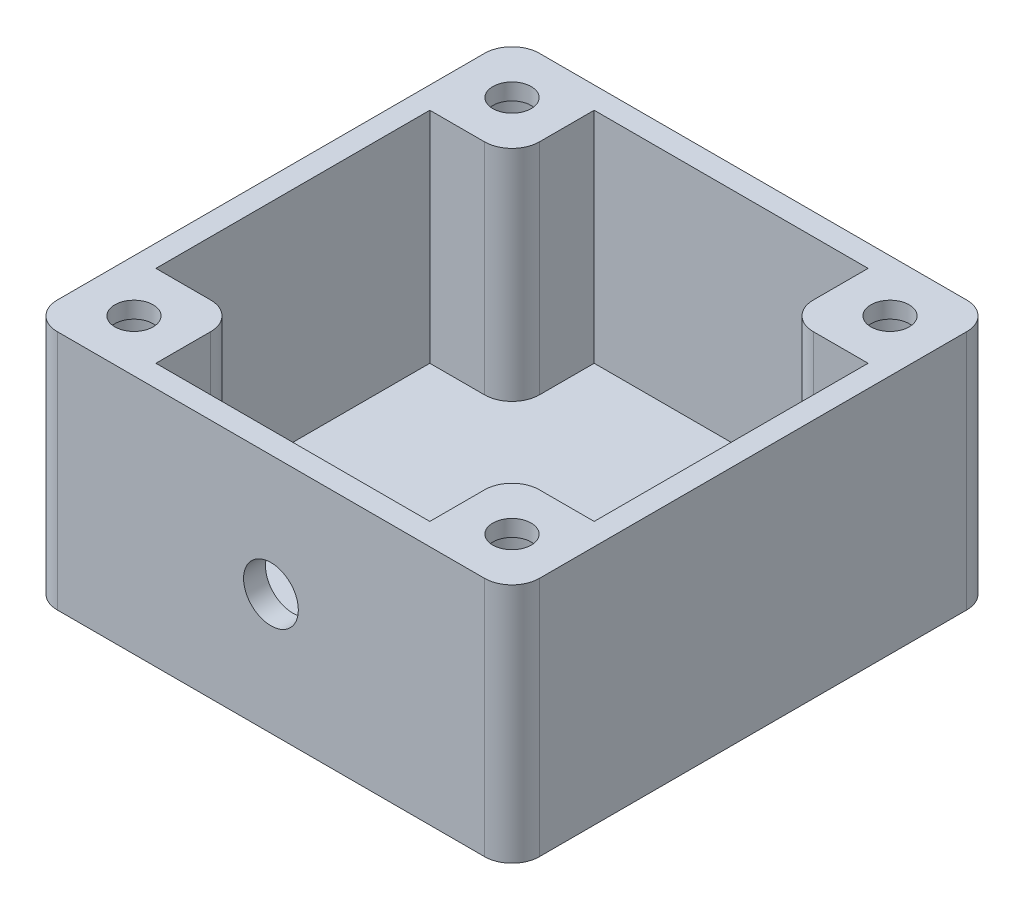
SolidWorks part; units mm, degrees
ref_plane "Front" through (0, 0, 0) normal (0, 0, 1) x (1, 0, 0)
ref_plane "Top" through (0, 0, 0) normal (0, 1, 0) x (1, 0, 0)
ref_plane "Right" through (0, 0, 0) normal (1, 0, 0) x (0, 0, -1)
sketch "Sketch1" plane through (0, 0, 0) normal (0, 1, 0) x (1, 0, 0)
  line L1 (-12.5, -20) -> (12.5, -20)
  line L2 (-12.5, -20) -> (-12.5, 20)
  line L3 (-12.5, 20) -> (12.5, 20)
  line L4 (12.5, -20) -> (12.5, 20)
  line L5 (-12.5, -20) -> (12.5, 20) construction
  line L6 (-12.5, 20) -> (12.5, -20) construction
  line L7 (-22, -22) -> (22, -22)
  line L8 (-22, -22) -> (-22, 22)
  line L9 (-22, 22) -> (22, 22)
  line L10 (22, -22) -> (22, 22)
  line L11 (-22, -22) -> (22, 22) construction
  line L12 (-22, 22) -> (22, -22) construction
  point P0 (0, 0)
  point P10 (0, 0)
  dimension "45" = 40
  dimension "D6" = 25
  dimension "D7" = 9.5
  dimension "D8" = 2
extrude "Boss-Extrude4" add sketch "Sketch1" along normal blind 20
sketch "Sketch4" plane through (0, 0, 0) normal (0, -1, 0) x (1, 0, 0)
  line L1 (22, -22) -> (-22, -22)
  line L2 (22, -22) -> (22, 22)
  line L3 (22, 22) -> (-22, 22)
  line L4 (-22, -22) -> (-22, 22)
  line L5 (22, -22) -> (-22, 22) construction
  line L6 (22, 22) -> (-22, -22) construction
  point P0 (0, 0)
extrude "Boss-Extrude5" add sketch "Sketch4" along normal blind 2
sketch "Sketch5" plane through (0, 0, 0) normal (0, 1, 0) x (1, 0, 0)
  line L0 (-3.8714, -6.8383) -> (-1.43, -7.7269)
  line L1 (0, 0) -> (0, -18.2319) construction
  line L2 (0, 0) -> (-2.9072, -7.9874) construction
  circle A0 centre (0, 0) radius 3.45
  arc A1 (-3.8714, -6.8383) -> (-1.43, -7.7269) centre (-2.9072, -7.9874) ccw
  dimension "D1" = 6.9
  dimension "D3" = 3
  dimension "D2" = 8.5
  dimension "D5" = 0.75
  dimension "D4" = 20
extrude "Cut-Extrude2" cut sketch "Sketch5" against normal blind 2
sketch "Sketch6" plane through (0, 20, 0) normal (0, 1, 0) x (1, 0, 0)
  line L0 (0, 22) -> (0, -22) construction
  line L1 (22, 22) -> (-22, 22) construction
  line L2 (-22, -22) -> (22, -22) construction
  line L3 (-12.5, -20) -> (-22, -20) construction
  line L4 (-22, 22) -> (-22, -22) construction
  line L5 (-17.25, -20) -> (-17.25, 22) construction
  circle A0 centre (-17.25, 17.25) radius 1.75
  circle A1 centre (-17.25, -17.25) radius 1.75
  dimension "D2" = 3.5
  dimension "D1" = 4.75
  dimension "D3" = 4.75
  dimension "D4" = 4.75
extrude "Cut-Extrude3" cut sketch "Sketch6" against normal through all
mirror "Mirror1" about plane through (0, 0, 0) normal (1, 0, 0) of "Cut-Extrude3"
sketch "Sketch7" plane through (0, -2, 0) normal (0, -1, 0) x (1, 0, 0)
  circle A0 centre (-17.25, 17.25) radius 3.25
  circle A1 centre (17.25, 17.25) radius 3.25
  circle A2 centre (17.25, -17.25) radius 3.25
  circle A3 centre (-17.25, -17.25) radius 3.25
  point P11 (-17.25, -17.25)
  point P13 (-17.25, -17.25)
  point P14 (-17.25, -17.25)
  point P15 (-18.5, -18.5)
  point P16 (0, 0)
  point P17 (0, 0)
  point P18 (-22.25, -22.25)
  point P20 (0, 0)
  point P21 (0, 0)
  dimension "D1" = 6.5
extrude "Cut-Extrude4" cut sketch "Sketch7" against normal offset from surface (20.5 mm away) 1.5 up to face at (17.25, 20, -15.5)
sketch "Sketch10" plane through (0, 20, 0) normal (0, 1, 0) x (1, 0, 0)
  line L0 (-12.5, 20) -> (-12.5, -20) construction
  line L1 (-12.5, 12.5) -> (-20, 12.5)
  line L2 (-12.5, 12.5) -> (-12.5, -12.5)
  line L3 (-12.5, -12.5) -> (-20, -12.5)
  line L4 (-20, 12.5) -> (-20, -12.5)
  line L5 (-22, 22) -> (-22, -22) construction
  line L7 (-22, 22) -> (22, 22) construction
  line L8 (12.5, 20) -> (-12.5, 20) construction
  circle A0 centre (-17.25, 17.25) radius 1.75 construction
  circle A1 centre (-17.25, -17.25) radius 1.75 construction
  dimension "D3" = 4.75
  dimension "D1" = 2
  dimension "D2" = 2
  dimension "D4" = 4.75
  dimension "D5" = 4.75
extrude "Cut-Extrude5" cut sketch "Sketch10" against normal up to surface (20 mm away) up to face at (0, 0, 3.45)
mirror "Mirror2" about plane through (0, 0, 0) normal (1, 0, 0) of "Cut-Extrude5"
sketch "Sketch11" plane through (0, 0, 22) normal (0, 0, 1) x (1, 0, 0)
  line L0 (-22, 9) -> (22, 9) construction
  line L1 (-22, 20) -> (-22, -2) construction
  line L2 (22, 20) -> (22, -2) construction
  circle A0 centre (0, 9) radius 2.5
  dimension "D1" = 5
extrude "Cut-Extrude6" cut sketch "Sketch11" against normal up to next
fillet "Fillet1" radius 2.5 8 edges at (-22, 9, 22) (22, 9, 22) (22, 9, -22) (12.5, 10, 12.5) (-12.5, 10, 12.5) (12.5, 10, -12.5) (-12.5, 10, -12.5) (-22, 9, -22)
equation "\"D1@Sketch6\"=\"D3@Sketch6\""
equation "\"D4@Sketch6\"=\"D3@Sketch6\""
equation "\"D1@Sketch10\"=\"D2@Sketch10\""
equation "\"D4@Sketch10\"=\"D3@Sketch10\""
equation "\"D5@Sketch10\"=\"D4@Sketch10\""
equation "\"D7@Sketch1\" =  ( \"45@Sketch1\" + 2 * \"D8@Sketch1\" - \"D6@Sketch1\" )  / 2"
equation "\"D5@Sketch5\"=\"D3@Sketch5\"/4"
